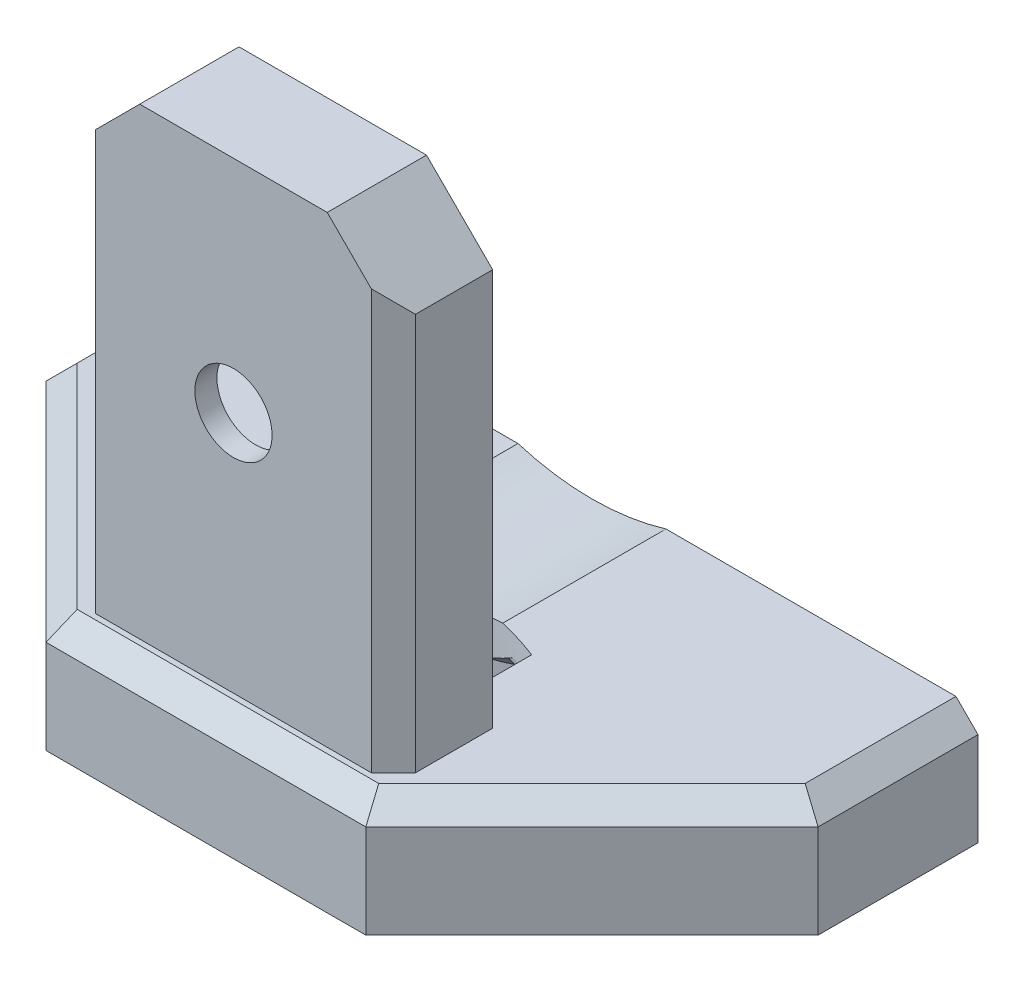
SolidWorks part; units mm, degrees
material "PLA"
ref_plane "Front Plane" through (0, 0, 0) normal (0, 0, 1) x (1, 0, 0)
ref_plane "Top Plane" through (0, 0, 0) normal (0, 1, 0) x (1, 0, 0)
ref_plane "Right Plane" through (0, 0, 0) normal (1, 0, 0) x (0, 0, -1)
sketch "Sketch1" plane through (0, 0, 0) normal (0, 1, 0) x (1, 0, 0)
  line L0 (-35, 0) -> (35, 0)
  line L3 (-35, 0) -> (-35, -14.4975)
  line L4 (-35, -14.4975) -> (-14.4975, -35)
  line L5 (-14.4975, -35) -> (14.4975, -35)
  line L6 (14.4975, -35) -> (35, -14.4975)
  line L7 (35, -14.4975) -> (35, 0)
  line L10 (22.7681, 72.2656) -> (2.2656, 51.7631) [skipped]
  line L11 (-18.1173, 67.6148) -> (-38.6199, 88.1173) [skipped]
  line L12 (67.199, 35) -> (9.2091, 35) [skipped]
  arc A0 (-35, 0) -> (35, 0) centre (0, 0) ccw construction
  dimension "D1" = 35
extrude "Boss-Extrude1" add sketch "Sketch1" along normal blind 10.5
sketch "Sketch2" plane through (0, 10.5, 0) normal (0, 1, 0) x (1, 0, 0)
  line L0 (-14.4975, -35) -> (14.4975, -35) construction
  line L1 (-14.5, -32.5) -> (14.5, -32.5)
  line L2 (-14.5, -32.5) -> (-14.5, -23.5)
  line L3 (-14.5, -23.5) -> (14.5, -23.5)
  line L4 (14.5, -32.5) -> (14.5, -23.5)
  point P4 (0, -23.5)
  dimension "D1" = 9
  dimension "D2" = 2.5
  dimension "D3" = 29
extrude "Boss-Extrude2" add sketch "Sketch2" along normal blind 42
sketch "Sketch3" plane through (0, 0, 0) normal (0, 0, -1) x (-1, 0, 0)
  line L0 (-27, 0) -> (-27, 3)
  line L1 (-35, 0) -> (35, 0) construction
  line L2 (-27, 3) -> (-29, 3)
  line L3 (-29, 7.5) -> (0, 7.5)
  line L4 (0, 0) -> (0, 11.6654) construction
  line L5 (-35, 10.5) -> (-35, 0) construction
  line L6 (-30, 4) -> (-30, 6.5)
  line L7 (-30, 6.5) -> (-29, 7.5)
  line L8 (-29, 3) -> (-30, 4)
  line L9 (-27, 0) -> (0, 0)
  line L10 (0, 0) -> (0, 7.5)
  point P5 (-30, 3)
  point P6 (-30, 7.5)
  dimension "D1" = 8
  dimension "D2" = 4.5
  dimension "D3" = 3
  dimension "D4" = 3
revolve "Cut-Revolve1" cut sketch "Sketch3" angle 180 about L4
sketch "Sketch4" plane through (0, 0, 35) normal (0, 0, 1) x (1, 0, 0)
  line L0 (-14.4975, 0) -> (14.4975, 0) construction
  circle A0 centre (0, 32.5) radius 3.5
  point P7 (0, 0)
  dimension "D1" = 7
  dimension "D2" = 32.5
extrude "Cut-Extrude1" cut sketch "Sketch4" against normal up to next
chamfer "Chamfer1" distance 6 angle 45 2 edges at (14.5, 52.5, 28) (-14.5, 52.5, 28)
chamfer "Chamfer2" distance 2 angle 45 7 edges at (35, 10.5, 7.2487) (24.7487, 10.5, 24.7487) (-24.7487, 10.5, 24.7487) (-35, 10.5, 7.2487) (14.5, 28.5, 32.5) (-14.5, 28.5, 32.5) (0, 10.5, 35)
sketch "Sketch5" plane through (0, 7.5, 0) normal (0, -1, 0) x (1, 0, 0)
  line L0 (24, 0) -> (-24, 0)
  line L1 (29, 0) -> (-29, 0) construction
  line L2 (-21.365, 3) -> (-12, 4.147)
  line L3 (-12, 4.147) -> (-6.125, 4.147)
  line L4 (-4.125, 6.147) -> (-4.125, 12.022)
  line L5 (-4.125, 12.022) -> (-2.978, 21.387)
  line L6 (0, -5.775) -> (0, 5.775) construction
  line L7 (4.125, 12.022) -> (2.978, 21.387)
  line L8 (4.125, 6.147) -> (4.125, 12.022)
  line L9 (12, 4.147) -> (6.125, 4.147)
  line L10 (21.365, 3) -> (12, 4.147)
  arc A0 (-24, 0) -> (-21.365, 3) centre (-20.9747, 0) cw
  arc A1 (-6.125, 4.147) -> (-4.125, 6.147) centre (-6.125, 6.147) ccw
  arc A2 (2.978, 21.387) -> (-2.978, 21.387) centre (0, 21.387) ccw
  arc A3 (6.125, 4.147) -> (4.125, 6.147) centre (6.125, 6.147) cw
  arc A4 (24, 0) -> (21.365, 3) centre (20.9747, 0) ccw
  point P4 (0, 0)
  dimension "D2" = 3
  dimension "D6" = 2
  dimension "D10" = 2.635
  dimension "D1" = 48
  dimension "D3" = 9.365
  dimension "D4" = 1.147
  dimension "D5" = 5.875
  dimension "D7" = 5.875
  dimension "D8" = 9.365
  dimension "D9" = 1.147
extrude "Cut-Extrude2" cut sketch "Sketch5" against normal blind 1
sketch "Sketch6" plane through (0, 7.5, 0) normal (0, -1, 0) x (1, 0, 0)
  line L9 (21.365, 3) -> (12, 4.147)
  line L10 (12, 4.147) -> (6.125, 4.147)
  line L11 (4.125, 6.147) -> (4.125, 12.022)
  line L12 (4.125, 12.022) -> (2.978, 21.387)
  line L13 (-2.978, 21.387) -> (-4.125, 12.022)
  line L14 (-4.125, 12.022) -> (-4.125, 6.147)
  line L15 (-6.125, 4.147) -> (-12, 4.147)
  line L16 (-12, 4.147) -> (-21.365, 3)
  line L17 (-24, 0) -> (24, 0)
  line L18 (14.4999, 3.8408) -> (12, 4.147)
  line L19 (12, 4.147) -> (6.125, 4.147)
  line L20 (4.125, 6.147) -> (4.125, 12.022)
  line L21 (4.125, 12.022) -> (3.8209, 14.5052)
  line L22 (-3.8209, 14.5052) -> (-4.125, 12.022)
  line L23 (-4.125, 12.022) -> (-4.125, 6.147)
  line L24 (-6.125, 4.147) -> (-12, 4.147)
  line L25 (-12, 4.147) -> (-14.4999, 3.8408)
  arc A0 (14.4999, 3.8408) -> (3.8209, 14.5052) centre (0, 0) ccw
  arc A1 (-3.8209, 14.5052) -> (-14.4999, 3.8408) centre (0, 0) ccw
  arc A5 (24, 0) -> (21.365, 3) centre (20.9747, 0) ccw
  arc A6 (4.125, 6.147) -> (6.125, 4.147) centre (6.125, 6.147) ccw
  arc A7 (2.978, 21.387) -> (-2.978, 21.387) centre (0, 21.387) ccw
  arc A8 (-6.125, 4.147) -> (-4.125, 6.147) centre (-6.125, 6.147) ccw
  arc A9 (-21.365, 3) -> (-24, 0) centre (-20.9747, 0) ccw
  arc A11 (4.125, 6.147) -> (6.125, 4.147) centre (6.125, 6.147) ccw
  arc A13 (-6.125, 4.147) -> (-4.125, 6.147) centre (-6.125, 6.147) ccw
  dimension "D2" = 30
  dimension "D1" = 0
extrude "Boss-Extrude3" add sketch "Sketch6" along normal blind 6.5
chamfer "Chamfer3" distance 1 angle 45 2 edges at (10.5993, 7.5, 10.6139) (-10.5993, 7.5, 10.6139)
sketch "Sketch7" plane through (0, 0, 23.5) normal (0, 0, -1) x (-1, 0, 0)
  line L0 (-10.5, 24.8351) -> (-10.5, 10.5)
  line L1 (10.5, 40.1649) -> (10.5, 44.8431)
  line L15 (-10.5, 10.5) -> (10.5, 10.5)
  line L20 (10.5, 10.5) -> (10.5, 44.8431)
  line L21 (10.5, 44.8431) -> (6.8431, 48.5)
  line L22 (6.8431, 48.5) -> (-6.8431, 48.5)
  line L23 (-6.8431, 48.5) -> (-10.5, 44.8431)
  line L24 (-10.5, 44.8431) -> (-10.5, 10.5)
  line L25 (10.5, 10.5) -> (10.5, 24.8351)
  line L26 (10.5, 44.8431) -> (6.8431, 48.5)
  line L27 (6.8431, 48.5) -> (-6.8431, 48.5)
  line L28 (-6.8431, 48.5) -> (-10.5, 44.8431)
  line L29 (-10.5, 44.8431) -> (-10.5, 40.1649)
  arc A0 (10.5, 24.8351) -> (10.5, 40.1649) centre (0, 32.5) ccw
  arc A1 (-10.5, 40.1649) -> (-10.5, 24.8351) centre (0, 32.5) ccw
  dimension "D2" = 26
  dimension "D1" = 4
extrude "Cut-Extrude3" cut sketch "Sketch7" against normal offset from surface (7 mm away) 2 up to face at (-3.5, 32.5, 32.5)
sketch "Sketch9" plane through (0, 10.5, 0) normal (0, 1, 0) x (1, 0, 0)
  line L7 (-10.5, -23.5) -> (-14.5, -23.5) construction
  line L8 (-13.5556, -21.5) -> (12.4041, -21.5) construction
  line L9 (-10.5, -27.0324) -> (-10.5, -15.9676)
  line L10 (10.5, -15.9676) -> (10.5, -27.0324)
  arc A0 (-29, 0) -> (29, 0) centre (0, 0) ccw construction
  arc A1 (-10.5, -27.0324) -> (10.5, -27.0324) centre (0, 0) ccw
  arc A3 (-10.5, -15.9676) -> (10.5, -15.9676) centre (0, -43) cw
  dimension "D2" = 21
  dimension "D1" = 2
extrude "Cut-Extrude5" cut sketch "Sketch9" against normal up to surface (3 mm away)
sketch "Sketch10" plane through (0, 0, 0) normal (0, 0, -1) x (-1, 0, 0)
  line L0 (-30, 6.5) -> (-30, 4) construction
  line L1 (-35, 8.5) -> (-35, 0) construction
  line L2 (0, 19.25) -> (0, -19.25) construction
  circle A0 centre (-32.5, 5.25) radius 1.45
  circle A1 centre (32.5, 5.25) radius 1.45
  point P5 (-30, 5.25)
  dimension "D1" = 2.9
  dimension "D2" = 2.5
extrude "Cut-Extrude6" cut sketch "Sketch10" against normal blind 10
fillet "Fillet6" radius 1 6 edges at (0, 10.5, 29) (-10.5, 7.5, 21.5) (10.5, 7.5, 21.5) (0, 8.5, 14) (8.4354, 7.5, 15.2539) (-8.4354, 7.5, 15.2539)
sketch "Sketch11" plane through (0, 10.5, 0) normal (0, 1, 0) x (1, 0, 0)
  point P0 (0, 0)
sketch "Sketch12" plane through (0, 0, 0) normal (0, 0, -1) x (-1, 0, 0)
  line L0 (-6.7082, 10.5) -> (6.7082, 10.5)
  line L1 (-33, 10.5) -> (33, 10.5) construction
  arc A0 (-6.7082, 10.5) -> (6.7082, 10.5) centre (0, 32.5) ccw
  dimension "D1" = 46
extrude "Cut-Extrude7" cut sketch "Sketch12" against normal up to next
sketch "Sketch13" plane through (0, 7.5, 0) normal (0, 1, 0) x (1, 0, 0)
  line L0 (-10.5, -15.9676) -> (10.5, -15.9676)
  arc A0 (10.5, -15.9676) -> (6.7082, -14.7865) centre (0, -43) ccw construction
  arc A1 (6.7082, -14.7865) -> (0, -14) centre (0, -43) ccw construction
  arc A2 (0, -14) -> (-6.7082, -14.7865) centre (0, -43) ccw construction
  arc A3 (-6.7082, -14.7865) -> (-10.5, -15.9676) centre (0, -43) ccw construction
  arc A4 (10.5, -15.9676) -> (6.7082, -14.7865) centre (0, -43) ccw
  arc A5 (6.7082, -14.7865) -> (0, -14) centre (0, -43) ccw
  arc A6 (0, -14) -> (-6.7082, -14.7865) centre (0, -43) ccw
  arc A7 (-6.7082, -14.7865) -> (-10.5, -15.9676) centre (0, -43) ccw
extrude "Cut-Extrude8" cut sketch "Sketch13" against normal through all
